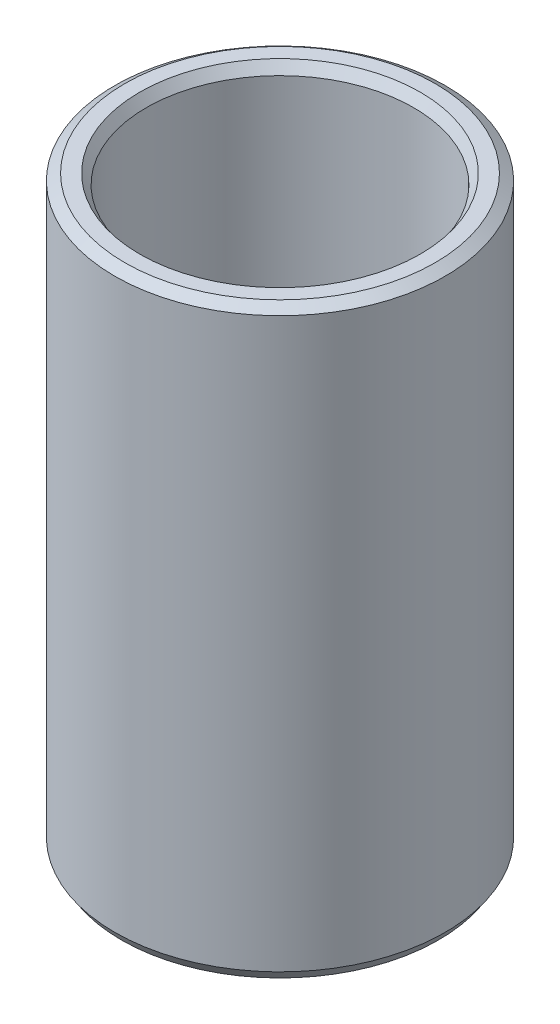
SolidWorks part; units mm, degrees
ref_plane "Front Plane" through (0, 0, 0) normal (0, 0, 1) x (1, 0, 0)
ref_plane "Top Plane" through (0, 0, 0) normal (0, 1, 0) x (1, 0, 0)
ref_plane "Right Plane" through (0, 0, 0) normal (1, 0, 0) x (0, 0, -1)
sketch "Sketch1" plane through (0, 0, 0) normal (0, 1, 0) x (1, 0, 0)
  circle A0 centre (0, 0) radius 40
  dimension "SLEEVE_OD" = 80
extrude "Boss-Extrude1" add sketch "Sketch1" along normal blind 141.6316
sketch "Sketch2" plane through (0, 0, 0) normal (0, 1, 0) x (1, 0, 0)
  circle A0 centre (0, 0) radius 32.3529
  dimension "BORE_D" = 64.7059
extrude "Cut-Extrude1" cut sketch "Sketch2" along normal through all
chamfer "Chamfer1" distance 1.6184 angle 56.31 4 edges at (0, 141.6316, 32.3529) (0, 0, 32.3529) (0, 0, 40) (0, 141.6316, 40) first distance on face at (0, 141.6316, 32.3529) first distance on face at (0, 0, 32.3529) first distance on face at (0, 141.6316, 40)
